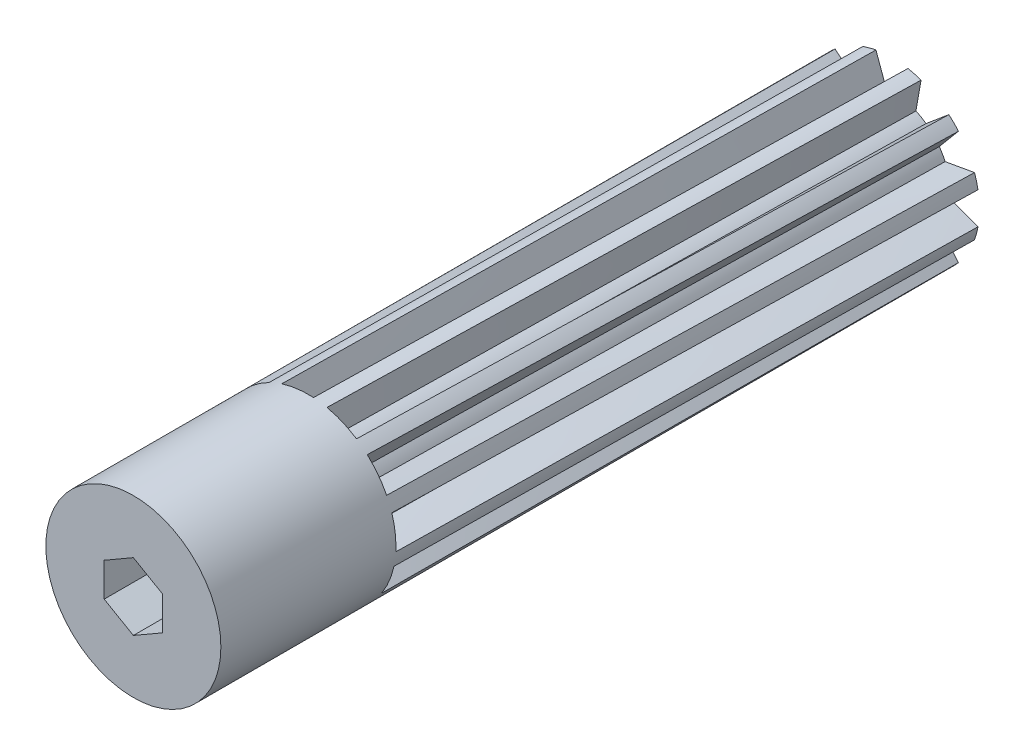
SolidWorks part; units mm, degrees
ref_plane "Front Plane" through (0, 0, 0) normal (0, 0, 1) x (1, 0, 0)
ref_plane "Top Plane" through (0, 0, 0) normal (0, 1, 0) x (1, 0, 0)
ref_plane "Right Plane" through (0, 0, 0) normal (1, 0, 0) x (0, 0, -1)
sketch "Sketch1" plane through (0, 0, 0) normal (0, 0, 1) x (1, 0, 0)
  line L1 (5, 2.8868) -> (0, 5.7735)
  line L2 (0, 5.7735) -> (-5, 2.8868)
  line L3 (-5, 2.8868) -> (-5, -2.8868)
  line L4 (-5, -2.8868) -> (0, -5.7735)
  line L5 (0, -5.7735) -> (5, -2.8868)
  line L6 (5, -2.8868) -> (5, 2.8868)
  circle A0 centre (0, 0) radius 5 construction
  circle A1 centre (0, 0) radius 15
  dimension "D1" = 10
  dimension "D2" = 30
extrude "Boss-Extrude2" add sketch "Sketch1" against normal blind 130 contours A1
extrude "Cut-Extrude1" cut sketch "Sketch1<4>" against normal through all contours L3 L4 L5 L6 L1 L2
sketch "Sketch1<4>" plane through (0, 0, 0) normal (0, 0, 1) x (1, 0, 0) same geometry as "Sketch1"
sketch "Sketch4" plane through (0, 0, -130) normal (0, 0, -1) x (-1, 0, 0)
  circle A0 centre (0, 0) radius 15 construction
  circle A1 centre (0, 0) radius 15
curve "Helix/Spiral1" pitch 5000 height 100 radius 15 centre (0, 0, -130) axis (0, 0, 1) start towards (0, 1, 0)
sketch "Sketch6" plane through (0, 0, -130) normal (0, 0, 1) x (1, 0, 0)
  line L0 (0, 0) -> (0, 27.1802) construction
  line L1 (-2.7458, 14.7465) -> (-1, 9.9499)
  line L2 (2.7458, 14.7465) -> (1, 9.9499)
  arc A0 (1, 9.9499) -> (-1, 9.9499) centre (0, 0) ccw
  circle A1 centre (0, 0) radius 15
  arc A2 (2.7458, 14.7465) -> (-2.7458, 14.7465) centre (0, 0) ccw
  dimension "D2" = 5
  dimension "D3" = 1
  dimension "D4" = 20
  dimension "D1" = 0
sweep "Cut-Sweep1" cut profiles "Sketch6" path "Helix/Spiral1" align with end faces yes
pattern_circular "CirPattern2" count 12 over 360 about axis through (0, 0, -130) along (0, 0, 1) of "Cut-Sweep1"
